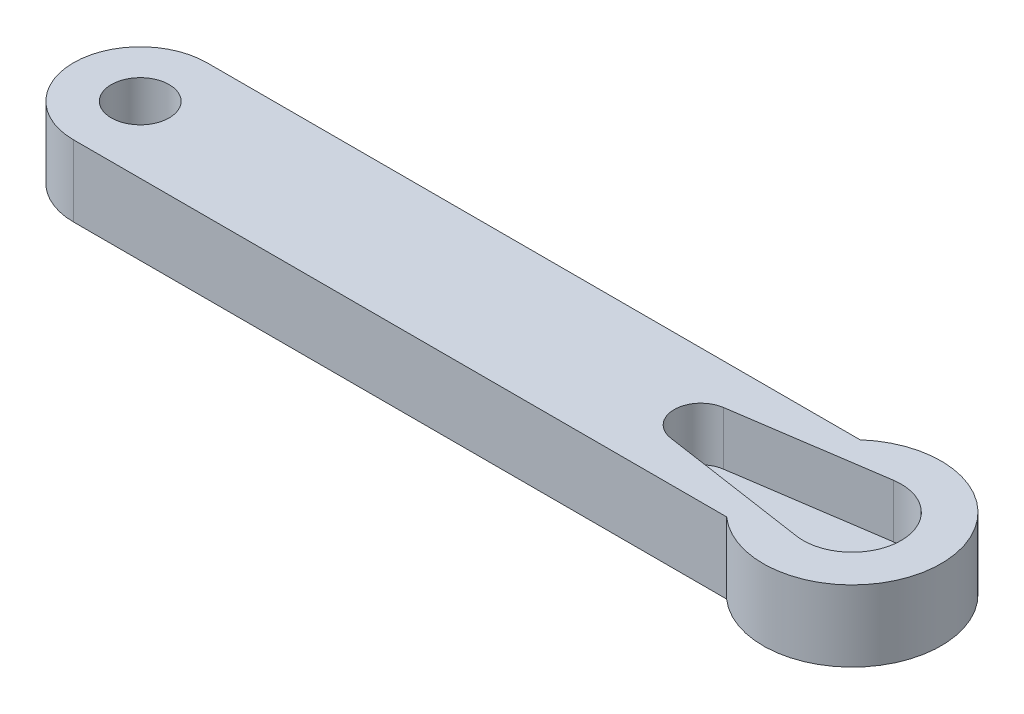
SolidWorks part; units mm, degrees
ref_plane "Front Plane" through (0, 0, 0) normal (0, 0, 1) x (1, 0, 0)
ref_plane "Top Plane" through (0, 0, 0) normal (0, 1, 0) x (1, 0, 0)
ref_plane "Right Plane" through (0, 0, 0) normal (1, 0, 0) x (0, 0, -1)
sketch "Sketch3" plane through (0, 0, 0) normal (0, 1, 0) x (1, 0, 0)
  line L0 (-7.8549, -22.0079) -> (-24.8549, -22.0079)
  line L1 (-87.8549, -14.5079) -> (-7.8549, -14.5079)
  line L2 (-87.8549, -14.5079) -> (-87.8549, -29.5079)
  line L3 (-87.8549, -29.5079) -> (-7.8549, -29.5079)
  line L4 (-7.8549, -14.5079) -> (-7.8549, -29.5079)
  line L5 (-25.2961, -19.0405) -> (-8.6638, -16.5677)
  line L6 (-25.2961, -24.9753) -> (-8.6638, -27.4481)
  line L7 (-25.2961, -19.0405) -> (-25.2961, -24.9753)
  circle A0 centre (-87.8549, -22.0079) radius 3.25
  circle A1 centre (-87.8549, -22.0079) radius 7.5
  circle A2 centre (-7.8549, -22.0079) radius 10
  circle A3 centre (-7.8549, -22.0079) radius 2.4248
  circle A4 centre (-7.8549, -22.0079) radius 5.5
  circle A5 centre (-24.8549, -22.0079) radius 3
  arc A6 (-87.8549, -25.2579) -> (-87.8549, -18.7579) centre (-87.8549, -22.0079) ccw
  dimension "D1" = 15
  dimension "D2" = 6.5
  dimension "D4" = 20
  dimension "D5" = 11
  dimension "D7" = 6
  dimension "D3" = 80
  dimension "D6" = 17
extrude "Boss-Extrude4" add sketch "Sketch3" along normal blind 8 contours L2 A1 A0 | L2 A1 A0 | A5 L5 A2 L1 A1 L3 L6 | A4 L6 A2 L3 L4 | A4 L4 L1 A2 L5 | A4 L4 L3 A2 L1 region at (-12.1993, 0, 15.8994) region at (-7.5949, 0, 15.5079) region at (-12.1993, 0, 28.1163) region at (-51.3921, 0, 22.0079) region at (-84.2548, 0, 22.0079) region at (-91.455, 0, 22.0079)
extrude "Boss-Extrude5" add sketch "Sketch3<24>" along normal blind 2 separate body contours L0 A4 L4 A3 | L4 A4 L0 A3 | L4 A4 A3 | A5 L0 A2 L5 | A4 L5 A2 L0 | L7 A5 | A5 L7 | A5 L6 A2 L0 | A4 L0 A2 L6 region at (-10.5041, 0, 24.6571) region at (-10.5041, 0, 19.3587) region at (-5.2058, 0, 22.0079) region at (-14.8081, 0, 24.4929) region at (-14.8081, 0, 19.5228) region at (-20.0638, 0, 24.0742) region at (-20.0638, 0, 19.9416) region at (-22.941, 0, 24.2275) region at (-26.3697, 0, 22.0079)
sketch "Sketch3<24>" plane through (0, 0, 0) normal (0, 1, 0) x (1, 0, 0) same geometry as "Sketch3"
